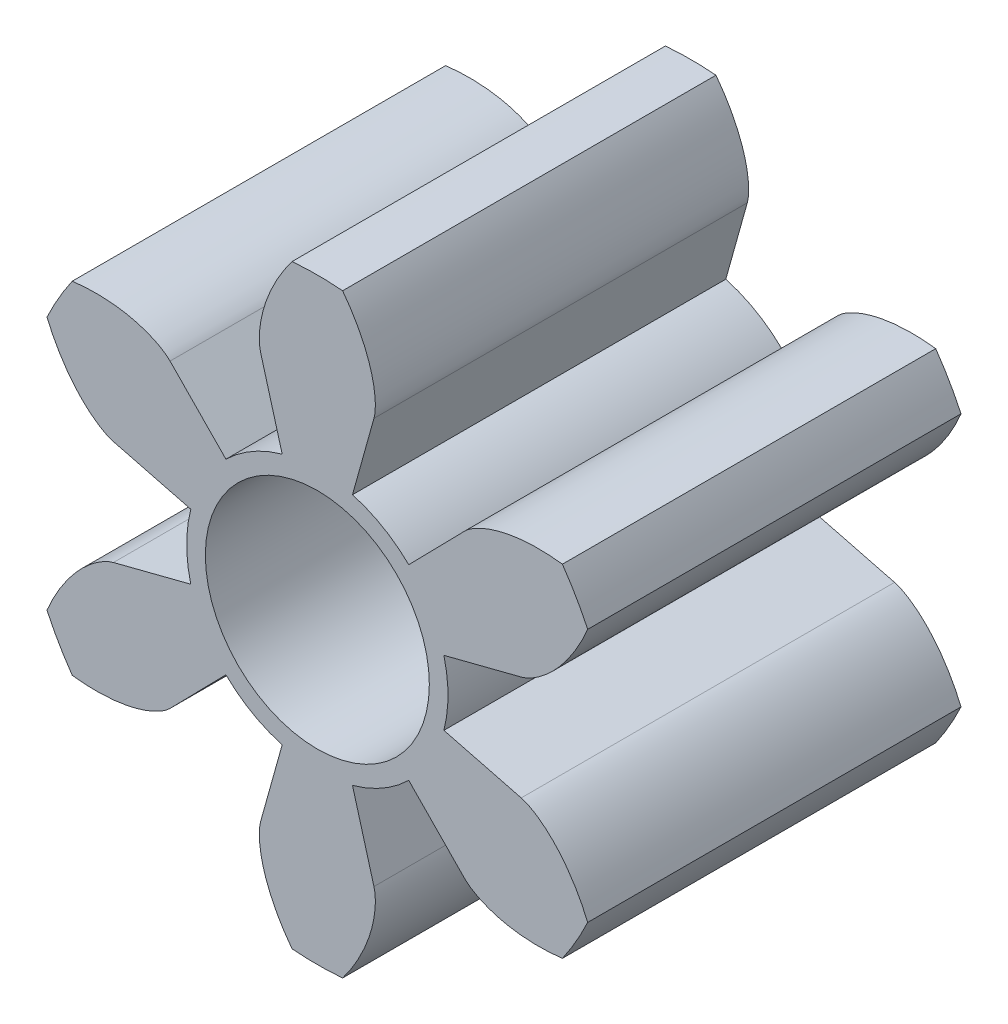
SolidWorks part; units mm, degrees
ref_plane "前视基准面" through (0, 0, 0) normal (0, 0, 1) x (1, 0, 0)
ref_plane "上视基准面" through (0, 0, 0) normal (0, 1, 0) x (1, 0, 0)
ref_plane "右视基准面" through (0, 0, 0) normal (1, 0, 0) x (0, 0, -1)
other "Configuration Table"
sketch "草图1" plane through (0, 0, 0) normal (0, 0, 1) x (1, 0, 0)
  line L0 (0, 0) -> (3, 0) construction
  line L1 (0, 0) -> (2.8978, 0.7765) construction
  line L2 (0, 0) -> (2.7305, 0.701)
  line L3 (2.8978, 0.7765) -> (2.8978, -0.7765) construction
  line L4 (0, 0) -> (2.7305, -0.701)
  circle A0 centre (0, 0) radius 4
  circle A1 centre (0, 0) radius 3 construction
  circle A2 centre (0, 0) radius 1.75
  circle A3 centre (0, 0) radius 2.8191 construction
  circle A4 centre (0, 0) radius 1.5
  spline S0 degree 4 poles (2.7305, 0.701) (2.7514, 0.7063) (2.8083, 0.7255) (2.9105, 0.779) (3.0627, 0.8875) (3.236, 1.0573) (3.4253, 1.3046) (3.6012, 1.6247) (3.742, 2.0003) (3.8364, 2.4221) (3.8779, 2.852) (3.8707, 3.2837) (3.8157, 3.7334) (3.69, 4.2802) (3.4574, 4.9086) (3.0836, 5.5918) (2.5556, 6.2772) (1.9356, 6.8796) (1.2391, 7.3923) (0.4849, 7.8122) (-0.3175, 8.1368) (-1.1468, 8.3674) (-2.0054, 8.5023) (-2.7502, 8.5427) (-3.4127, 8.5171) (-3.8849, 8.4708) (-4.3024, 8.4076) (-4.5772, 8.3558) (-4.9624, 8.2714) (-5.2496, 8.1908) (-5.5362, 8.1071) (-5.6783, 8.056) (-5.7704, 8.0254) knots 0 0 0 0 0 0.005604 0.015718 0.02996 0.048734 0.068727 0.096889 0.125051 0.153212 0.181374 0.209535 0.237696 0.271429 0.327752 0.384075 0.440398 0.496721 0.553044 0.609367 0.66569 0.722013 0.778336 0.834659 0.86282 0.890982 0.909091 0.931818 0.954545 0.977273 1 1 1 1 1 construction
  spline S1 degree 4 poles (2.7305, 0.701) (2.7514, 0.7063) (2.8083, 0.7255) (2.9105, 0.779) (3.0627, 0.8875) (3.236, 1.0573) (3.4253, 1.3046) (3.6012, 1.6247) (3.742, 2.0003) (3.8364, 2.4221) (3.8779, 2.852) (3.8707, 3.2837) (3.8157, 3.7334) (3.69, 4.2802) (3.4574, 4.9086) (3.0836, 5.5918) (2.5556, 6.2772) (1.9356, 6.8796) (1.2391, 7.3923) (0.4849, 7.8122) (-0.3175, 8.1368) (-1.1468, 8.3674) (-2.0054, 8.5023) (-2.7502, 8.5427) (-3.4127, 8.5171) (-3.8849, 8.4708) (-4.2047, 8.4224) (-4.3632, 8.395) (-4.4251, 8.3835) knots 0 0 0 0 0 0.005604 0.015718 0.02996 0.048734 0.068727 0.096889 0.125051 0.153212 0.181374 0.209535 0.237696 0.271429 0.327752 0.384075 0.440398 0.496721 0.553044 0.609367 0.66569 0.722013 0.778336 0.834659 0.86282 0.890982 0.909091 0.909091 0.909091 0.909091 0.909091
  spline S2 degree 4 poles (2.7305, -0.701) (2.7514, -0.7063) (2.8083, -0.7255) (2.9105, -0.779) (3.0627, -0.8875) (3.236, -1.0573) (3.4253, -1.3046) (3.6012, -1.6247) (3.742, -2.0003) (3.8364, -2.4221) (3.8779, -2.852) (3.8707, -3.2837) (3.8157, -3.7334) (3.69, -4.2802) (3.4574, -4.9086) (3.0836, -5.5918) (2.5556, -6.2772) (1.9356, -6.8796) (1.2391, -7.3923) (0.4849, -7.8122) (-0.3175, -8.1368) (-1.1468, -8.3674) (-2.0054, -8.5023) (-2.7502, -8.5427) (-3.4127, -8.5171) (-3.8849, -8.4708) (-4.3024, -8.4076) (-4.5772, -8.3558) (-4.9624, -8.2714) (-5.2496, -8.1908) (-5.5362, -8.1071) (-5.6783, -8.056) (-5.7704, -8.0254) knots 0 0 0 0 0 0.005604 0.015718 0.02996 0.048734 0.068727 0.096889 0.125051 0.153212 0.181374 0.209535 0.237696 0.271429 0.327752 0.384075 0.440398 0.496721 0.553044 0.609367 0.66569 0.722013 0.778336 0.834659 0.86282 0.890982 0.909091 0.931818 0.954545 0.977273 1 1 1 1 1 construction
  spline S3 degree 4 poles (2.7305, -0.701) (2.7514, -0.7063) (2.8083, -0.7255) (2.9105, -0.779) (3.0627, -0.8875) (3.236, -1.0573) (3.4253, -1.3046) (3.6012, -1.6247) (3.742, -2.0003) (3.8364, -2.4221) (3.8779, -2.852) (3.8707, -3.2837) (3.8157, -3.7334) (3.69, -4.2802) (3.4574, -4.9086) (3.0836, -5.5918) (2.5556, -6.2772) (1.9356, -6.8796) (1.2391, -7.3923) (0.4849, -7.8122) (-0.3175, -8.1368) (-1.1468, -8.3674) (-2.0054, -8.5023) (-2.7502, -8.5427) (-3.4127, -8.5171) (-3.8849, -8.4708) (-4.2047, -8.4224) (-4.3632, -8.395) (-4.4251, -8.3835) knots 0 0 0 0 0 0.005604 0.015718 0.02996 0.048734 0.068727 0.096889 0.125051 0.153212 0.181374 0.209535 0.237696 0.271429 0.327752 0.384075 0.440398 0.496721 0.553044 0.609367 0.66569 0.722013 0.778336 0.834659 0.86282 0.890982 0.909091 0.909091 0.909091 0.909091 0.909091
  point P15 (2.8978, 0)
  dimension "齿顶圆直径" = 8
  dimension "分度圆直径" = 6
  dimension "齿根圆直径" = 3.5
  dimension "基圆直径" = 5.6382
  dimension "内孔直径" = 3
  dimension "渐近线镜像线夹角" = 15
extrude "凸台-拉伸1" add sketch "草图1" along normal blind 5 contours A0 | A4
extrude "切除-拉伸1" cut sketch "草图1<3>" along normal through all contours A2 S3 A0 S1 region at (3.0753, 0, 0)
sketch "草图1<3>" plane through (0, 0, 0) normal (0, 0, 1) x (1, 0, 0) same geometry as "草图1"
pattern_circular "阵列(圆周)1" count 6 every 60 about axis through (0, 0, 5) along (0, 0, 1) of "切除-拉伸1"
equation "\"m\"= 1'模数"
equation "\"z\"= 6'齿数"
equation "\"a\"= 20度'压力角"
equation "\"d\"= \"m\" * \"z\"'分度圆直径"
equation "\"da\"= ( \"z\" + 2 ) * \"m\"'齿顶圆直径"
equation "\"df\"= ( \"z\" - 2.5 ) * \"m\"'齿根圆直径"
equation "\"s\"= 0.5 * PI * \"m\"'分度圆齿厚"
equation "\"r\"= 0.38 * \"m\"'齿根圆角"
equation "\"B\"= 0.3 * \"d\"'齿厚"
equation "\"db\"= \"m\" * \"z\" * cos ( \"a\" )'基圆直径"
equation "\"rb\"= \"db\" / 2'基圆半径"
equation "\"齿顶圆直径@草图1\"= \"da\""
equation "\"分度圆直径@草图1\"= \"d\""
equation "\"齿根圆直径@草图1\"= \"df\""
equation "\"基圆直径@草图1\"= \"db\""
equation "\"渐近线镜像线夹角@草图1\"= 360 / 4 / \"z\""
equation "\"h\"= 5'齿轮厚度"
equation "\"ir\"= 3'内孔直径"
equation "\"内孔直径@草图1\"= \"ir\""
equation "\"齿轮厚@凸台-拉伸1\"= \"h\""
equation "\"齿轮夹角@阵列(圆周)1\"= 360 / \"z\""
equation "\"齿数@阵列(圆周)1\"= \"z\""
